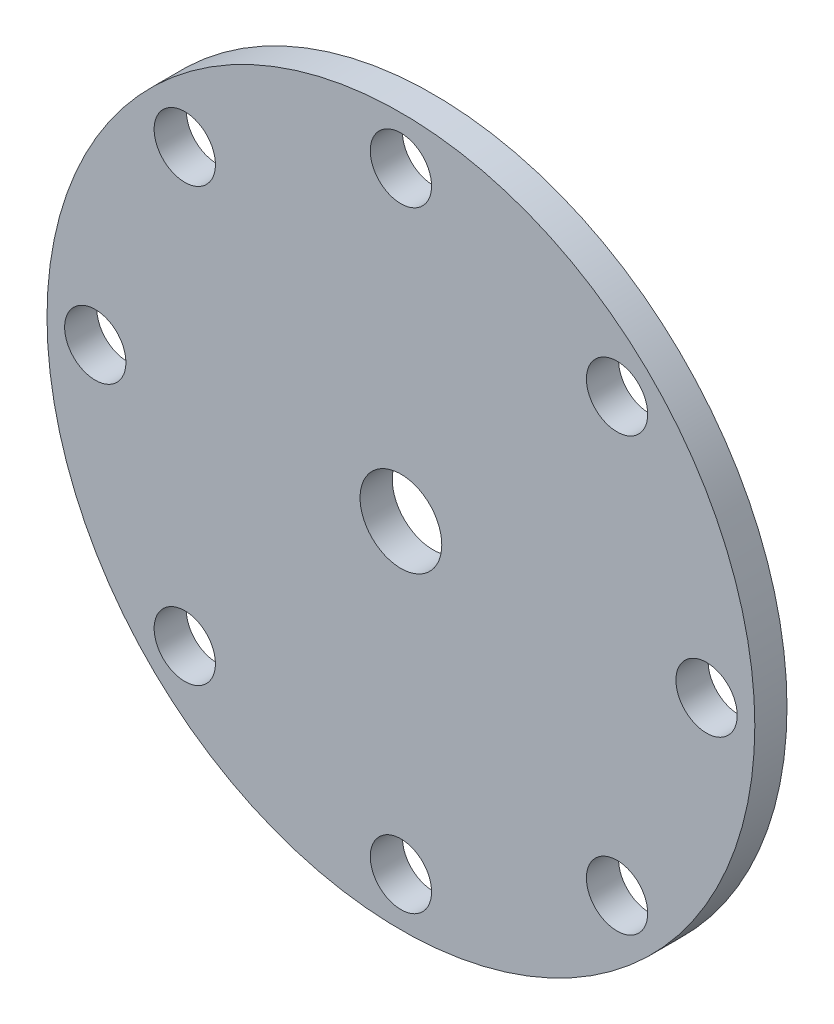
SolidWorks part; units mm, degrees
ref_plane "Front Plane" through (0, 0, 0) normal (0, 0, 1) x (1, 0, 0)
ref_plane "Top Plane" through (0, 0, 0) normal (0, 1, 0) x (1, 0, 0)
ref_plane "Right Plane" through (0, 0, 0) normal (1, 0, 0) x (0, 0, -1)
sketch "Sketch1" plane through (0, 0, 0) normal (0, 0, 1) x (1, 0, 0)
  line L0 (0, 55) -> (0, -55) construction
  line L1 (-55, 0) -> (55, 0) construction
  line L2 (-33.5876, 33.5876) -> (33.5876, -33.5876) construction
  line L3 (-33.5876, -33.5876) -> (33.5876, 33.5876) construction
  circle A0 centre (0, 0) radius 55
  circle A1 centre (0, 0) radius 6.35
  circle A2 centre (0, 47.5) radius 4.7625
  circle A6 centre (33.5876, 33.5876) radius 4.7625
  circle A7 centre (47.5, 0) radius 4.7625
  circle A8 centre (33.5876, -33.5876) radius 4.7625
  circle A9 centre (0, -47.5) radius 4.7625
  circle A10 centre (-33.5876, -33.5876) radius 4.7625
  circle A11 centre (-47.5, 0) radius 4.7625
  circle A12 centre (-33.5876, 33.5876) radius 4.7625
  dimension "D1" = 110
  dimension "D2" = 12.7
  dimension "D3" = 9.525
  dimension "D6" = 47.5
  dimension "D4" = 47.5
  dimension "D5" = 8
extrude "Rotor Disc" add sketch "Sketch1" along normal blind 5 contours A0 A12 A11 A10 A8 A7 A6 A1 A2 region at (-53.4444, 0, 0)
